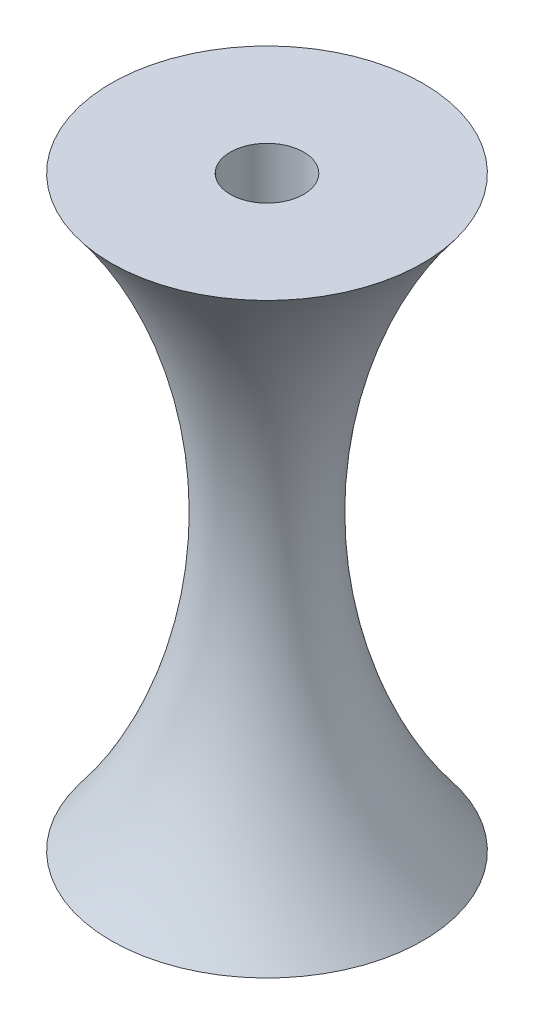
SolidWorks part; units mm, degrees
ref_plane "Front Plane" through (0, 0, 0) normal (0, 0, 1) x (1, 0, 0)
ref_plane "Top Plane" through (0, 0, 0) normal (0, 1, 0) x (1, 0, 0)
ref_plane "Right Plane" through (0, 0, 0) normal (1, 0, 0) x (0, 0, -1)
sketch "Sketch1" plane through (0, 0, 0) normal (0, 0, 1) x (1, 0, 0)
  line L0 (0, 16) -> (0, -16)
  line L1 (0, 16) -> (-3, 16)
  line L2 (-3, 16) -> (-8.5, 16)
  line L3 (-3, 16) -> (-3, -16)
  line L4 (-3, -16) -> (0, -16)
  line L5 (-3, -16) -> (-8.5, -16)
  arc A0 (-8.5, 16) -> (-8.5, -16) centre (-29.0227, 0) cw
  point P4 (0, 0)
  dimension "D1" = 32
  dimension "D2" = 3
  dimension "D3" = 5.5
revolve "Revolve1" add sketch "Sketch1" angle 360 about L0 region at (-1.5, 0, 0) region at (-4.6151, 12.0895, 0) region at (-4.6151, -12.0895, 0)
sketch "Sketch2" plane through (0, 16, 0) normal (0, 1, 0) x (1, 0, 0)
  circle A0 centre (0, 0) radius 2
  dimension "D1" = 4
extrude "Cut-Extrude1" cut sketch "Sketch2" against normal through all
sketch "Sketch3" plane through (0, 16, 0) normal (0, 1, 0) x (1, 0, 0)
  circle A0 centre (0, 0) radius 2.5
  point P3 (0, 0)
  dimension "D1" = 5
extrude "Cut-Extrude2" cut sketch "Sketch3" against normal blind 24 from offset 4 offset against normal yes
fillet "Fillet1" radius 0.5 2 edges at (0, -12, 2.5) (0, 12, 2.5)
